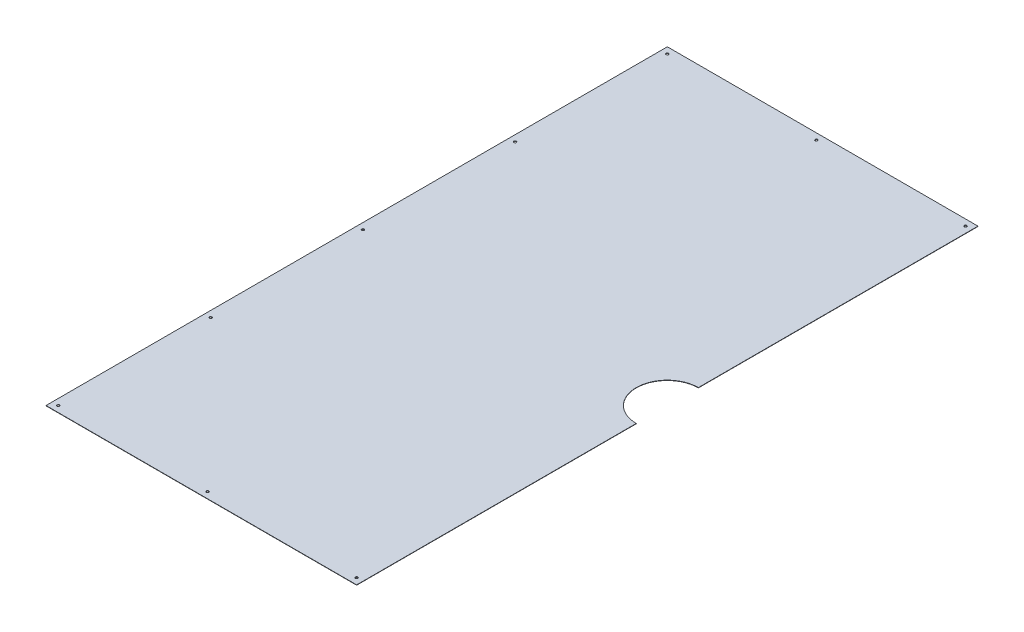
SolidWorks part; units mm, degrees
ref_plane "Front Plane" through (0, 0, 0) normal (0, 0, 1) x (1, 0, 0)
ref_plane "Top Plane" through (0, 0, 0) normal (0, 1, 0) x (1, 0, 0)
ref_plane "Right Plane" through (0, 0, 0) normal (1, 0, 0) x (0, 0, -1)
sketch "Sketch1" plane through (0, 0, 0) normal (0, 1, 0) x (1, 0, 0)
  line L7 (-500, -1000) -> (500, -1000)
  line L8 (-500, -1000) -> (-500, 1000)
  line L9 (-500, 1000) -> (500, 1000)
  line L11 (-500, -1000) -> (500, 1000) construction
  line L12 (-500, 1000) -> (500, -1000) construction
  line L13 (500, -1000) -> (500, -100)
  line L14 (500, 100) -> (500, 1000)
  line L15 (-480, -980) -> (480, -980) construction
  line L16 (-480, 980) -> (480, 980) construction
  arc A2 (500, 100) -> (500, -100) centre (500, 0) ccw
  circle A3 centre (-480, 490) radius 3
  circle A4 centre (-480, -980) radius 3
  circle A5 centre (480, -980) radius 3
  circle A8 centre (480, 980) radius 3
  circle A9 centre (-480, 980) radius 3
  circle A10 centre (-480, 0) radius 3
  circle A11 centre (-480, -490) radius 3
  circle A12 centre (0, -980) radius 3
  circle A13 centre (0, 980) radius 3
  point P0 (0, 0)
  dimension "D3" = 6
  dimension "D1" = 2000
  dimension "D2" = 6
  dimension "D4" = 6
  dimension "D5" = 6
  dimension "D6" = 6
  dimension "D7" = 6
  dimension "D8" = 6
  dimension "D9" = 6
extrude "Boss-Extrude1" add sketch "Sketch1" along normal blind 1 contours A2 L14 L9 L8 L7 L13 A12 A11 A10 A9 A8 A5 A4 A3 region at (-3.602, 0, 0)
chamfer "Chamfer1" distance 1 angle 45 9 edges at (480, 1, -977) (-480, 1, -977) (-480, 1, -487) (-480, 1, 3) (-480, 1, 493) (-480, 1, 983) (0, 1, 983) (480, 1, 983) (0, 1, -977)
